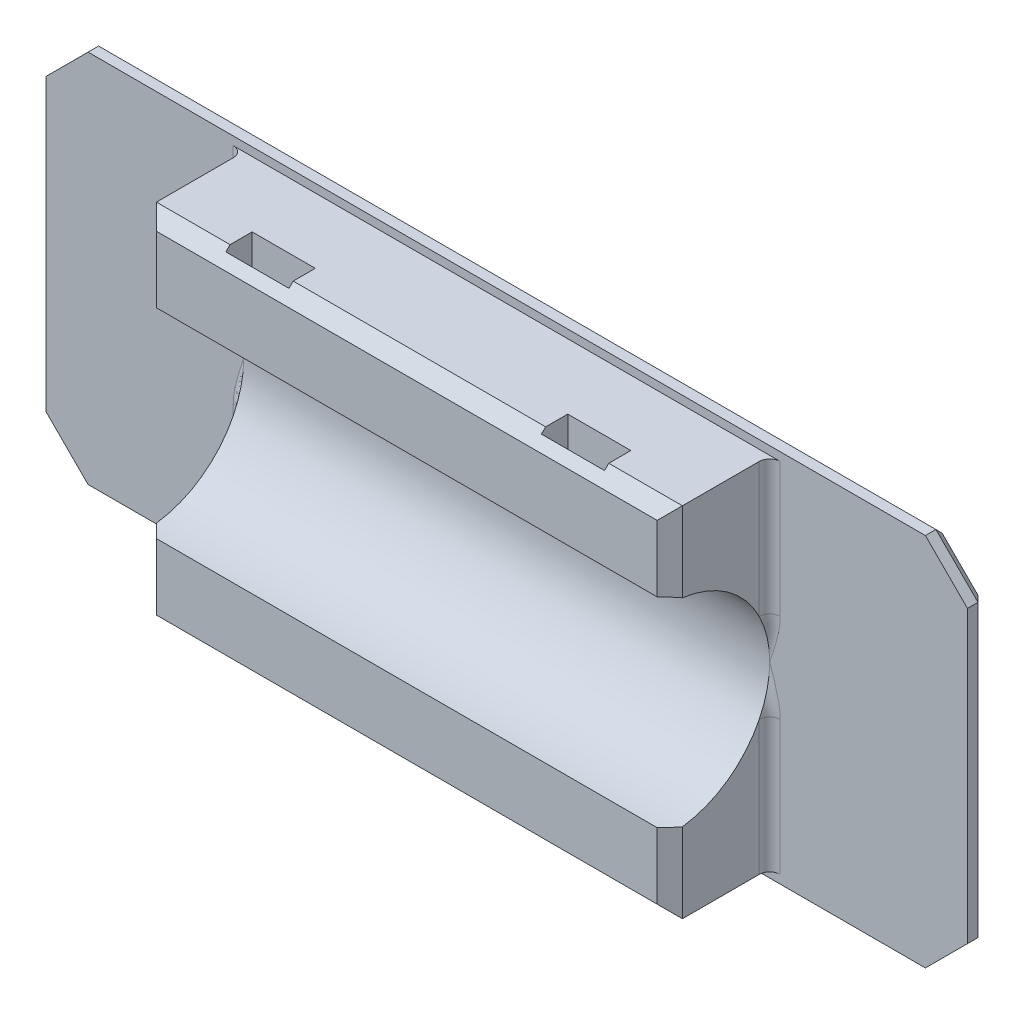
SolidWorks part; units mm, degrees
ref_plane "前基準面" through (0, 0, 0) normal (0, 0, 1) x (1, 0, 0)
ref_plane "上基準面" through (0, 0, 0) normal (0, 1, 0) x (1, 0, 0)
ref_plane "右基準面" through (0, 0, 0) normal (1, 0, 0) x (0, 0, -1)
sketch "草圖1" plane through (0, 0, 0) normal (0, 0, 1) x (1, 0, 0)
  line L1 (-43.8, 17.8) -> (43.8, 17.8)
  line L2 (-43.8, 17.8) -> (-43.8, -17.8)
  line L3 (-43.8, -17.8) -> (43.8, -17.8)
  line L4 (43.8, 17.8) -> (43.8, -17.8)
  point P4 (0, 17.8)
  point P6 (-43.8, 0)
  dimension "D1" = 87.6
  dimension "D2" = 35.6
extrude "填料-伸長1" add sketch "草圖1" along normal blind 2
chamfer "導角1" distance 4 angle 45 4 edges at (-43.8, 17.8, 1) (-43.8, -17.8, 1) (43.8, -17.8, 1) (43.8, 17.8, 1)
sketch "草圖2" plane through (0, 0, 2) normal (0, 0, 1) x (1, 0, 0)
  line L1 (-25, 17) -> (25, 17)
  line L2 (-25, 17) -> (-25, -17)
  line L3 (-25, -17) -> (25, -17)
  line L4 (25, 17) -> (25, -17)
  point P4 (0, 17)
  point P6 (-25, 0)
  dimension "D1" = 34
  dimension "D2" = 50
extrude "填料-伸長2" add sketch "草圖2" along normal blind 9.5
sketch "草圖3" plane through (25, 0, 0) normal (1, 0, 0) x (0, 0, -1)
  line L0 (-11.5, -17) -> (-11.5, 17) construction
  circle A0 centre (-11.5, 0) radius 9.5
  dimension "D1" = 19
extrude "除料-伸長1" cut sketch "草圖3" against normal through all
chamfer "導角2" distance 1 angle 45 8 edges at (-41.8, -15.8, 0) (0, -17.8, 0) (41.8, -15.8, 0) (43.8, 0, 0) (41.8, 15.8, 0) (0, 17.8, 0) (-41.8, 15.8, 0) (-43.8, 0, 0)
fillet "圓角1" radius 1 4 edges at (-25, 8.5, 2) (25, -8.5, 2) (-25, -8.5, 2) (25, 8.5, 2)
chamfer "導角3" distance 1.2 angle 45 6 edges at (-25, -13.25, 11.5) (25, -13.25, 11.5) (0, -17, 11.5) (-25, 13.25, 11.5) (25, 13.25, 11.5) (0, 17, 11.5)
sketch "草圖5" plane through (0, 0, 11.5) normal (0, 0, 1) x (1, 0, 0)
  line L1 (-25, 0) -> (25, 0) construction
  line L2 (0, 17) -> (0, -17) construction
  line L3 (-25, 17) -> (25, 17) construction
  line L4 (-26, -17) -> (26, -17) construction
  line L5 (-18, 13.2) -> (-18, 17)
  line L6 (-18, 17) -> (-12, 17)
  line L7 (-12, 17) -> (-12, 13.2)
  line L8 (12, 17) -> (12, 13.2)
  line L9 (18, 17) -> (12, 17)
  line L10 (18, 13.2) -> (18, 17)
  line L11 (18, -13.2) -> (18, -17)
  line L12 (18, -17) -> (12, -17)
  line L13 (12, -17) -> (12, -13.2)
  line L14 (-12, -17) -> (-12, -13.2)
  line L15 (-18, -17) -> (-12, -17)
  line L16 (-18, -13.2) -> (-18, -17)
  arc A0 (-18, 13.2) -> (-12, 13.2) centre (-15, 13.2) ccw
  arc A1 (18, 13.2) -> (12, 13.2) centre (15, 13.2) cw
  arc A2 (18, -13.2) -> (12, -13.2) centre (15, -13.2) ccw
  arc A3 (-18, -13.2) -> (-12, -13.2) centre (-15, -13.2) cw
  dimension "D1" = 6
  dimension "D2" = 3.8
  dimension "D3" = 15
extrude "除料-伸長3" cut sketch "草圖5" against normal blind 2.5 from offset 0.8 offset against normal yes
